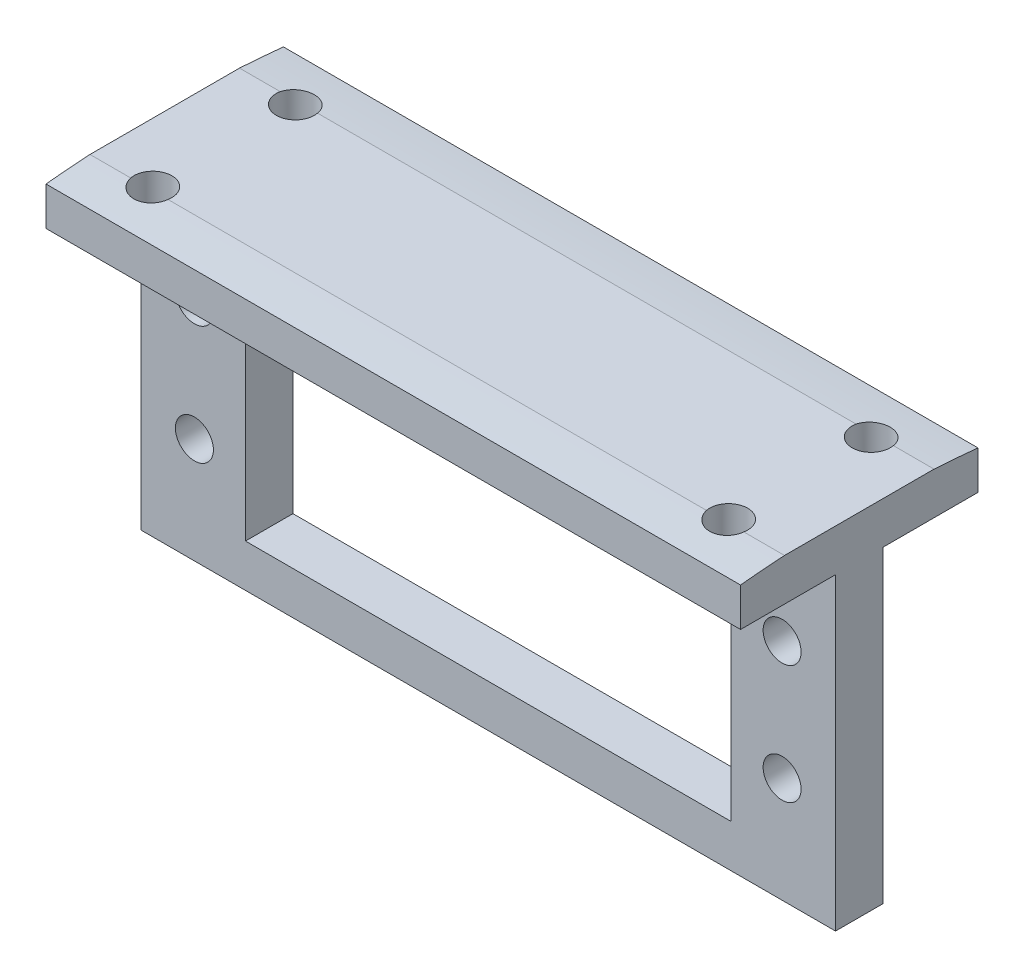
SolidWorks part; units mm, degrees
ref_plane "Front Plane" through (0, 0, 0) normal (0, 0, 1) x (1, 0, 0)
ref_plane "Top Plane" through (0, 0, 0) normal (0, 1, 0) x (1, 0, 0)
ref_plane "Right Plane" through (0, 0, 0) normal (1, 0, 0) x (0, 0, -1)
sketch "Web Sketch" plane through (0, 0, 0) normal (0, 0, 1) x (1, 0, 0)
  line L0 (-130.35, 69.5) -> (-71.85, 69.5)
  line L1 (-71.85, 69.5) -> (-71.85, 95.5)
  line L2 (-71.85, 95.5) -> (-130.35, 95.5)
  line L3 (-130.35, 95.5) -> (-130.35, 69.5)
extrude "Web" add sketch "Web Sketch" along normal mid plane 4
sketch "Flange Sketch" plane through (0, 0, 0) normal (0, 0, 1) x (1, 0, 0)
  line L0 (-130.35, 95.5) -> (-71.85, 95.5)
  line L1 (-71.85, 95.5) -> (-71.85, 99.05)
  line L2 (-71.85, 99.05) -> (-130.35, 99.05)
  line L3 (-130.35, 99.05) -> (-130.35, 95.5)
extrude "Flange" add sketch "Flange Sketch" along normal mid plane 20
ref_axis "Engine Axis" through (-68.925, 0, 0) along (-1, 0, 0)
sketch "Flange To Tube Sketch" plane through (0, 0, 0) normal (0, 0, 1) x (1, 0, 0)
  line L0 (-180.35, 0) -> (-21.85, 0) construction
  line L1 (-131.35, 99.25) -> (-70.85, 99.25)
  line L2 (-70.85, 99.25) -> (-70.85, 101.05)
  line L3 (-70.85, 101.05) -> (-131.35, 101.05)
  line L4 (-131.35, 101.05) -> (-131.35, 99.25)
revolve "Flange To Tube" cut sketch "Flange To Tube Sketch" angle 360 about L0
sketch "Servo Cutout Sketch" plane through (0, 0, 0) normal (0, 0, 1) x (1, 0, 0)
  line L0 (-121.55, 73.1) -> (-80.65, 73.1)
  line L1 (-80.65, 73.1) -> (-80.65, 93.7)
  line L2 (-80.65, 93.7) -> (-121.55, 93.7)
  line L3 (-121.55, 93.7) -> (-121.55, 73.1)
extrude "Servo Cutout" cut sketch "Servo Cutout Sketch" against normal mid plane 6
sketch "Servo Screw Holes Sketch" plane through (0, 0, 0) normal (0, 0, 1) x (1, 0, 0)
  circle A0 centre (-125.85, 78.4) radius 1.6
  circle A1 centre (-125.85, 88.4) radius 1.6
  circle A2 centre (-76.35, 78.4) radius 1.6
  circle A3 centre (-76.35, 88.4) radius 1.6
extrude "Servo Screw Holes" cut sketch "Servo Screw Holes Sketch" against normal mid plane 6
sketch "Tube Screw Holes Sketch" plane through (0, 0, 0) normal (0, 1, 0) x (1, 0, 0)
  circle A0 centre (-125.35, -6) radius 1.6
  circle A1 centre (-125.35, 6) radius 1.6
  circle A2 centre (-76.85, -6) radius 1.6
  circle A3 centre (-76.85, 6) radius 1.6
extrude "Tube Screw Holes" cut sketch "Tube Screw Holes Sketch" against normal mid plane 208.1
